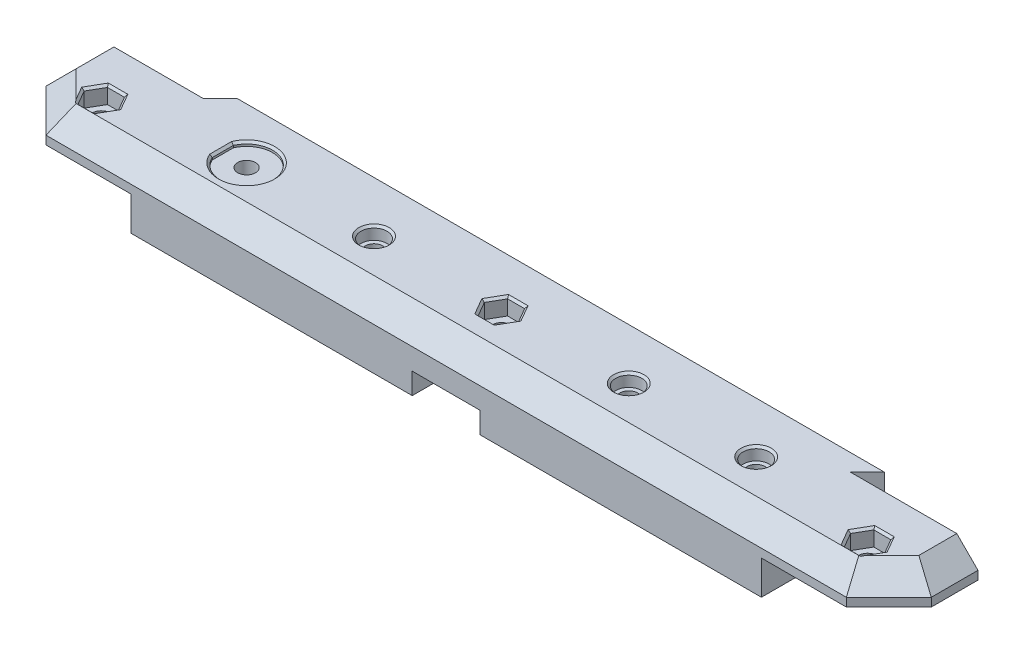
SolidWorks part; units mm, degrees
ref_plane "Front Plane" through (0, 0, 0) normal (0, 0, 1) x (1, 0, 0)
ref_plane "Top Plane" through (0, 0, 0) normal (0, 1, 0) x (1, 0, 0)
ref_plane "Right Plane" through (0, 0, 0) normal (1, 0, 0) x (0, 0, -1)
sketch "Sketch1" plane through (0, 0, 0) normal (0, 1, 0) x (1, 0, 0)
  line L0 (178.4924, 21) -> (208.4924, 21)
  line L1 (10, 0) -> (198.4924, 0)
  line L2 (0, 10) -> (0, 21)
  line L3 (0, 21) -> (30, 21)
  line L4 (208.4924, 10) -> (208.4924, 21)
  line L6 (30, 21) -> (30, 25)
  line L7 (30, 25) -> (178.4924, 25)
  line L8 (178.4924, 21) -> (178.4924, 25)
  line L9 (0, 10) -> (10, 0)
  line L10 (198.4924, 0) -> (208.4924, 10)
  line L11 (30, 25) -> (104.2462, -49.2462) construction
  line L12 (104.2462, -49.2462) -> (178.4924, 25) construction
  point P0 (0, 0)
  point P3 (208.4924, 0)
  dimension "D1" = 30
  dimension "D2" = 30
  dimension "D3" = 4
  dimension "D4" = 105
  dimension "D5" = 21
extrude "Main Base Extrude" add sketch "Sketch1" along normal blind 7
sketch "Sketch3" plane through (0, 0, 0) normal (0, 1, 0) x (1, 0, 0)
  line L0 (10, 0) -> (198.4924, 0) construction
  line L1 (30, 25) -> (178.4924, 25)
  line L2 (30, 25) -> (30, 0)
  line L3 (30, 0) -> (178.4924, 0)
  line L4 (178.4924, 25) -> (178.4924, 0)
extrude "Lower Base Extrude" add sketch "Sketch3" against normal blind 8
sketch "Sketch6" plane through (0, -8, 0) normal (0, -1, 0) x (1, 0, 0)
  line L0 (96.2462, 0) -> (112.2462, 0)
  line L1 (100.2462, -17) -> (108.2462, -17)
  line L2 (108.2462, -17) -> (112.2462, -10.0718)
  line L6 (96.2462, -10.0718) -> (100.2462, -17)
  line L7 (178.4924, -25) -> (30, -25) construction
  line L8 (30, 0) -> (178.4924, 0) construction
  line L9 (96.2462, -10.0718) -> (96.2462, 0)
  line L11 (112.2462, -10.0718) -> (112.2462, 0)
  line L14 (108.2462, -3.1436) -> (100.2462, -3.1436) [skipped]
  line L15 (100.2462, -3.1436) -> (96.2462, -10.0718) construction
  line L16 (112.2462, -10.0718) -> (108.2462, -3.1436) construction
  circle A0 centre (104.2462, -10.0718) radius 6.9282 construction
  point P13 (104.2462, 0)
  dimension "D1" = 8
  dimension "D2" = 8
  dimension "D3" = 16
extrude "Floor Tab Cut" cut sketch "Sketch6" against normal blind 5
chamfer "Main Body Chamfer" distance 5 angle 45 5 edges at (208.4924, 7, -15.5) (203.4924, 7, -5) (104.2462, 7, 0) (5, 7, -5) (0, 7, -15.5)
sketch "Sketch11" plane through (0, 7, 0) normal (0, 1, 0) x (1, 0, 0)
  line L0 (30, 21) -> (26, 25)
  line L1 (26, 25) -> (30, 25)
  line L2 (30, 25) -> (30, 21)
  line L3 (178.4924, 25) -> (182.4924, 21)
  line L4 (203.4924, 21) -> (178.4924, 21) construction
  line L5 (182.4924, 21) -> (178.4924, 21)
  line L6 (178.4924, 21) -> (178.4924, 25)
extrude "Column Chamfer-LF" [suppressed] add sketch "Sketch11" against normal up to surface (15 mm away) up to face at (104.2462, -8, -10.4144)
sketch "Sketch12" plane through (0, 7, 0) normal (0, 1, 0) x (1, 0, 0)
  line L0 (30, 25) -> (26, 21)
  line L1 (30, 21) -> (5, 21) construction
  line L2 (26, 21) -> (30, 21)
  line L3 (30, 21) -> (30, 25)
  line L4 (178.4924, 21) -> (182.4924, 25)
  line L5 (182.4924, 25) -> (178.4924, 25)
  line L6 (178.4924, 25) -> (178.4924, 21)
extrude "Column Chamfer-RF" add sketch "Sketch12" against normal up to surface (15 mm away) up to face at (104.2462, -8, -10.4144)
sketch "Sketch17" [suppressed] plane through (0, -8, 0) normal (0, -1, 0) x (1, 0, 0)
  line L0 (178.4924, -25) -> (178.4924, -21)
  line L1 (178.4924, -21) -> (182.4924, -21)
  line L2 (182.4924, -21) -> (178.4924, -25)
extrude "Corner column Edge Trim - LF" [suppressed] cut sketch "Sketch17" against normal up to surface (8 mm away) up to face at (194.4924, 0, -10.4)
sketch "Sketch16" plane through (0, -8, 0) normal (0, -1, 0) x (1, 0, 0)
  line L0 (30, -25) -> (30, -21)
  line L1 (30, -21) -> (26, -21)
  line L2 (26, -21) -> (30, -25)
extrude "Corner Column Edge Trim - RF" cut sketch "Sketch16" against normal up to surface (8 mm away) up to face at (16, 0, -12.1667)
sketch "Sketch2" plane through (0, 7, 0) normal (0, 1, 0) x (1, 0, 0)
  line L0 (-1000, 9) -> (49000, 9) construction
  line L3 (30, 25) -> (30, 21) construction
  line L4 (178.4924, 21) -> (178.4924, 25) construction
  line L5 (182.4924, 25) -> (30, 25) construction
  circle A0 centre (14, 9) radius 2.1
  circle A1 centre (194.4924, 9) radius 2.1
  dimension "4.2" = 4.2
  dimension "D2" = 16
  dimension "D3" = 16
  dimension "D4" = 16
extrude "Column Connect Holes" cut sketch "Sketch2" against normal through all
sketch "Sketch4" plane through (0, 7, 0) normal (0, 1, 0) x (1, 0, 0)
  line L0 (104.2462, -975) -> (104.2462, 49025) construction
  line L1 (182.4924, 25) -> (30, 25) construction
  line L2 (0, 21) -> (104.2462, 125.2462) construction
  line L3 (104.2462, 125.2462) -> (208.4924, 21) construction
  circle A0 centre (74.2462, 13) radius 2.1
  circle A1 centre (44.2462, 13) radius 2.1
  circle A2 centre (164.2462, 13) radius 2.1
  circle A3 centre (134.2462, 13) radius 2.1
  dimension "D1" = 4.2
  dimension "D2" = 30
  dimension "D3" = 30
  dimension "D4" = 12
extrude "Wall Connect Holes" cut sketch "Sketch4" against normal through all
sketch "Sketch8" plane through (0, -3, 0) normal (0, -1, 0) x (1, 0, 0)
  line L4 (112.2462, 0) -> (96.2462, 0) construction
  line L5 (182.4924, -25) -> (30, -25) construction
  circle A0 centre (104.2462, -13) radius 2
  point P4 (104.2462, 0)
  dimension "D1" = 4
  dimension "D2" = 12
extrude "Floor Tab Hole Cut" cut sketch "Sketch8" against normal through all
sketch "Sketch5" plane through (0, -8, 0) normal (0, -1, 0) x (1, 0, 0)
  circle A19 centre (44.2462, -13) radius 4
  circle A21 centre (134.2462, -13) radius 4
  circle A22 centre (164.2462, -13) radius 4
  circle A23 centre (74.2462, -13) radius 4
  dimension "D1" = 8
extrude "Wall Connect Hole Countersink" cut sketch "Sketch5" against normal blind 5
sketch "Sketch9" plane through (0, 7, 0) normal (0, 1, 0) x (1, 0, 0)
  line L1 (16.0063, 12.475) -> (11.9937, 12.475)
  line L2 (11.9937, 12.475) -> (9.9874, 9)
  line L3 (9.9874, 9) -> (11.9937, 5.525)
  line L4 (11.9937, 5.525) -> (16.0063, 5.525)
  line L5 (16.0063, 5.525) -> (18.0126, 9)
  line L6 (18.0126, 9) -> (16.0063, 12.475)
  line L7 (106.2525, 16.475) -> (102.2399, 16.475)
  line L8 (102.2399, 16.475) -> (100.2336, 13)
  line L9 (100.2336, 13) -> (102.2399, 9.525)
  line L10 (102.2399, 9.525) -> (106.2525, 9.525)
  line L11 (106.2525, 9.525) -> (108.2588, 13)
  line L12 (108.2588, 13) -> (106.2525, 16.475)
  line L13 (196.4987, 12.475) -> (192.4861, 12.475)
  line L14 (192.4861, 12.475) -> (190.4798, 9)
  line L15 (190.4798, 9) -> (192.4861, 5.525)
  line L16 (192.4861, 5.525) -> (196.4987, 5.525)
  line L17 (196.4987, 5.525) -> (198.505, 9)
  line L18 (198.505, 9) -> (196.4987, 12.475)
  circle A0 centre (14, 9) radius 3.475 construction
  circle A1 centre (104.2462, 13) radius 3.475 construction
  circle A2 centre (194.4924, 9) radius 3.475 construction
  dimension "D1" = 6.95
extrude "Nut Insert Cut" cut sketch "Sketch9" against normal blind 4
chamfer "Connect Hole Countersink Chamfer" distance 0.5 angle 45 4 edges at (164.2462, -8, -17) (134.2462, -8, -17) (74.2462, -8, -17) (44.2462, -8, -17)
chamfer "Nut Insert Chamfer" distance 0.5 angle 45 18 edges at (191.483, 7, -10.7375) (191.483, 7, -7.2625) (194.4924, 7, -5.525) (197.5019, 7, -7.2625) (197.5019, 7, -10.7375) (194.4924, 7, -12.475) (101.2368, 7, -14.7375) (101.2368, 7, -11.2625) (104.2462, 7, -9.525) (107.2557, 7, -11.2625) (107.2557, 7, -14.7375) (104.2462, 7, -16.475) (10.9906, 7, -10.7375) (10.9906, 7, -7.2625) (14, 7, -5.525) (17.0094, 7, -7.2625) (17.0094, 7, -10.7375) (14, 7, -12.475)
ref_plane "Mid Plane" through (104.2462, 0, 0) normal (1, 0, 0) x (0, 0, -1)
sketch "Sketch10" plane through (0, 7, 0) normal (0, 1, 0) x (1, 0, 0)
  line L0 (38.6462, 10.5189) -> (38.6462, 15.4811)
  arc A0 (38.6462, 10.5189) -> (38.6462, 15.4811) centre (44.2462, 13) ccw
  arc A3 (38.6462, 15.4811) -> (38.6462, 10.5189) centre (44.2462, 13) ccw construction
  dimension "D1" = 12.25
  dimension "D2" = 5.6
extrude "Door Peg Sink-RF" cut sketch "Sketch10" against normal blind 1
chamfer "Door Peg Chamfer - RF" distance 0.5 angle 45 2 edges at (38.6462, 7, -13) (50.3712, 7, -13)
sketch "Sketch13" [suppressed] plane through (0, 7, 0) normal (0, 1, 0) x (1, 0, 0)
  line L0 (169.8462, 10.5189) -> (169.8462, 15.4811)
  arc A0 (169.8462, 15.4811) -> (169.8462, 10.5189) centre (164.2462, 13) ccw
  arc A1 (169.8462, 10.5189) -> (169.8462, 15.4811) centre (164.2462, 13) ccw construction
  dimension "D1" = 12.25
  dimension "D2" = 5.6
extrude "Door Peg Sink - LF" [suppressed] cut sketch "Sketch13" against normal blind 1
chamfer "Door Peg Chamfer - LF" [suppressed] distance 0.5 angle 45
sketch "Sketch14" plane through (0, 7, 0) normal (0, 1, 0) x (1, 0, 0)
  circle A0 centre (134.2462, 13) radius 3.075
  circle A1 centre (74.2462, 13) radius 3.075
  circle A2 centre (164.2462, 13) radius 3.075
  dimension "D1" = 6.15
  dimension "D2" = 6.15
extrude "Magnet Hole Cut - RF" cut sketch "Sketch14" against normal blind 3
chamfer "Magnet Hole Chamfer - RF" distance 0.5 angle 45 3 edges at (74.2462, 7, -9.925) (134.2462, 7, -9.925) (164.2462, 7, -9.925)
sketch "Sketch18" [suppressed] plane through (0, 7, 0) normal (0, 1, 0) x (1, 0, 0)
  circle A0 centre (44.2462, 13) radius 3.075
  circle A1 centre (74.2462, 13) radius 3.075
  circle A2 centre (134.2462, 13) radius 3.075
  dimension "D1" = 6.15
extrude "Magnet Hole Cut - LF" [suppressed] cut sketch "Sketch18" against normal blind 3
chamfer "Magnet Hole Chamfer - LF" [suppressed] distance 0.5 angle 45
